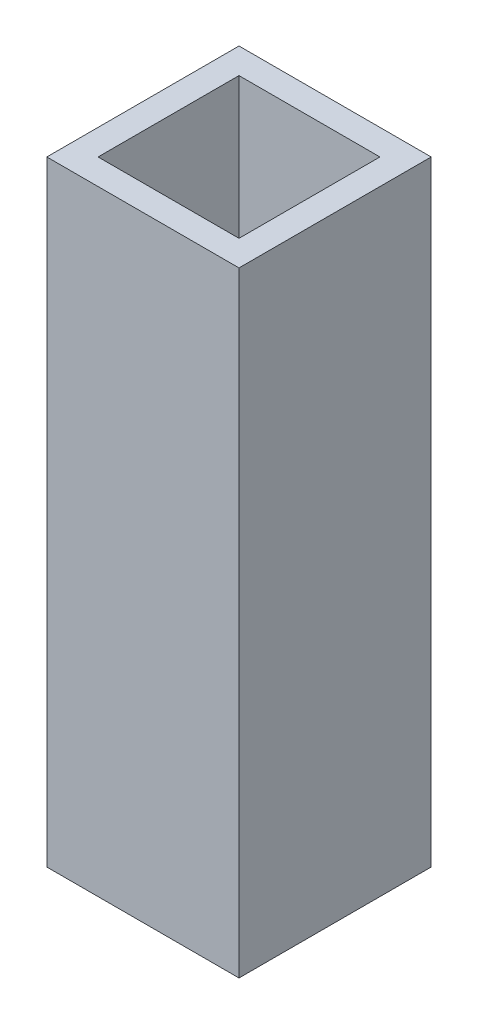
SolidWorks part; units mm, degrees
ref_plane "Front Plane" through (0, 0, 0) normal (0, 0, 1) x (1, 0, 0)
ref_plane "Top Plane" through (0, 0, 0) normal (0, 1, 0) x (1, 0, 0)
ref_plane "Right Plane" through (0, 0, 0) normal (1, 0, 0) x (0, 0, -1)
sketch "Sketch1" plane through (0, 0, 0) normal (0, 1, 0) x (1, 0, 0)
  line L0 (2, 2) -> (2, 13)
  line L1 (0, 0) -> (15, 0)
  line L2 (0, 0) -> (0, 15)
  line L3 (0, 15) -> (15, 15)
  line L4 (15, 0) -> (15, 15)
  line L5 (2, 13) -> (13, 13)
  line L6 (13, 2) -> (13, 13)
  line L7 (2, 2) -> (13, 2)
  dimension "D1" = 15
  dimension "D2" = 2
extrude "Boss-Extrude1" add sketch "Sketch1" along normal blind 48
